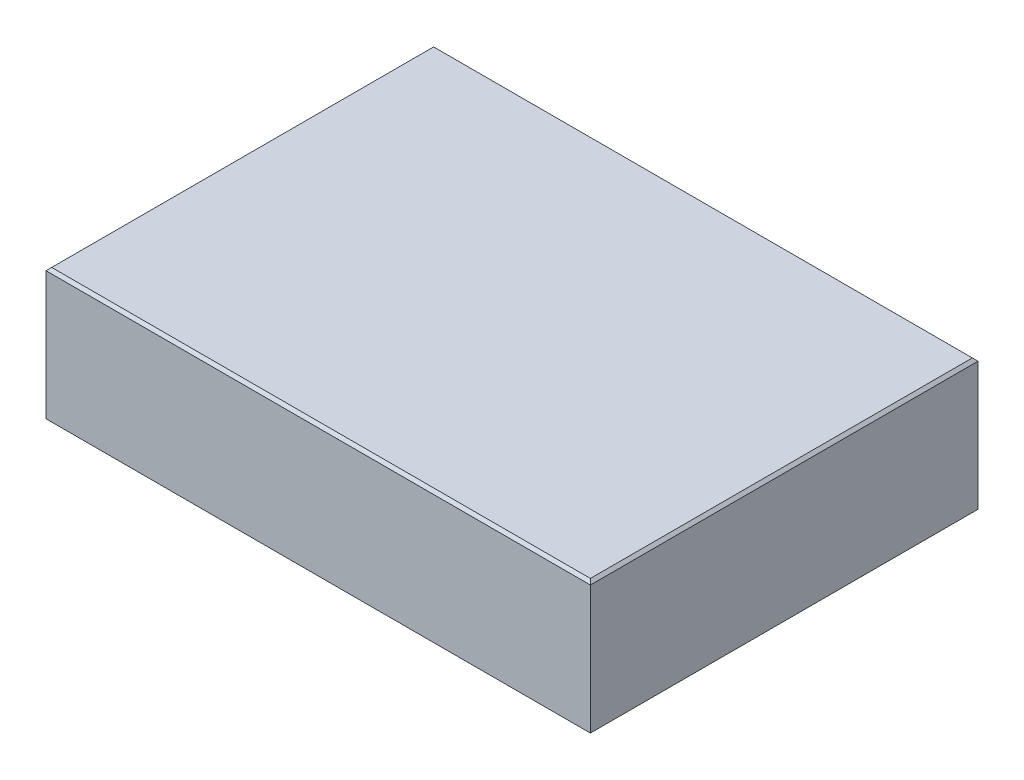
SolidWorks part; units mm, degrees
ref_plane "Front Plane" through (0, 0, 0) normal (0, 0, 1) x (1, 0, 0)
ref_plane "Top Plane" through (0, 0, 0) normal (0, 1, 0) x (1, 0, 0)
ref_plane "Right Plane" through (0, 0, 0) normal (1, 0, 0) x (0, 0, -1)
sketch "Sketch1" plane through (0, 0, 0) normal (0, 1, 0) x (1, 0, 0)
  line L1 (0, 0) -> (191, 0)
  line L2 (0, 0) -> (0, 136)
  line L3 (0, 136) -> (191, 136)
  line L4 (191, 0) -> (191, 136)
  dimension "D1" = 191
  dimension "D2" = 136
extrude "Boss-Extrude1" add sketch "Sketch1" along normal blind 46
sketch "Sketch3" plane through (0, 0, 0) normal (0, -1, 0) x (1, 0, 0)
  line L0 (0, -136) -> (0, 0) construction
  line L1 (5, -5) -> (186, -5)
  line L2 (5, -5) -> (5, -131)
  line L3 (5, -131) -> (186, -131)
  line L4 (186, -5) -> (186, -131)
  line L6 (191, -136) -> (0, -136) construction
  line L7 (191, 0) -> (191, -136) construction
  line L8 (0, 0) -> (191, 0) construction
  dimension "D1" = 5
  dimension "D2" = 5
  dimension "D3" = 5
  dimension "D4" = 5
extrude "Cut-Extrude1" cut sketch "Sketch3" against normal offset from surface (41 mm away) 5 contours L2 L3 L4 L1 up to face at (95.5, 46, -68)
chamfer "Chamfer1" distance 1 angle 45 4 edges at (0, 46, -68) (95.5, 46, -136) (191, 46, -68) (95.5, 46, 0)
